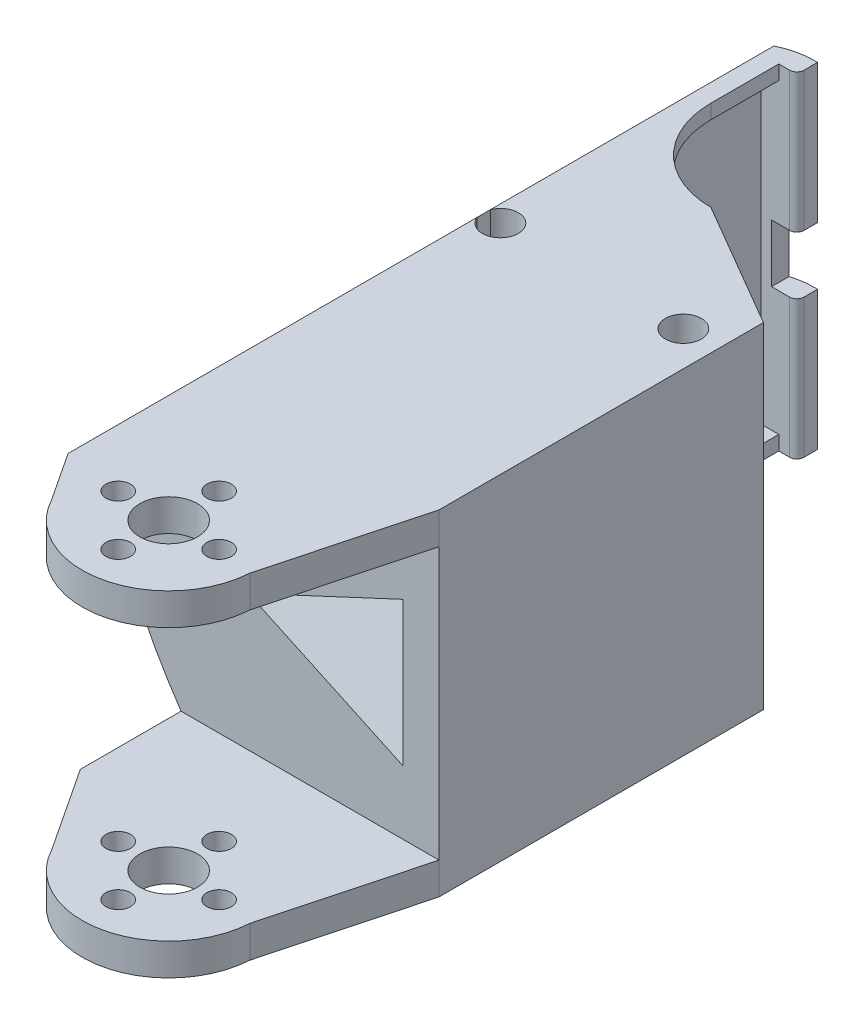
SolidWorks part; units mm, degrees
ref_plane "Front Plane" through (0, 0, 0) normal (0, 0, 1) x (1, 0, 0)
ref_plane "Top Plane" through (0, 0, 0) normal (0, 1, 0) x (1, 0, 0)
ref_plane "Right Plane" through (0, 0, 0) normal (1, 0, 0) x (0, 0, -1)
sketch "Sketch2" plane through (0, 0, 0) normal (0, 1, 0) x (1, 0, 0)
  line L0 (17.5, 0) -> (17.5, 37.7)
  line L1 (-15, 2.5) -> (15, 2.5)
  line L2 (-15, 2.5) -> (-15, 37.7)
  line L4 (15, 2.5) -> (15, 37.7)
  line L5 (17.5, 37.7) -> (15, 37.7)
  line L7 (-17.5, 37.7) -> (-17.5, 0)
  line L8 (-17.5, 0) -> (17.5, 0)
  line L10 (-17.5, 37.7) -> (-15, 37.7)
  point P4 (0, 2.5)
  point P12 (0, 0)
  dimension "D1" = 2.5
  dimension "D2" = 2.5
  dimension "D3" = 37.7
  dimension "D4" = 30
  dimension "D5" = 15
extrude "Boss-Extrude1" add sketch "Sketch2" along normal blind 32.5
sketch "Sketch4" plane through (0, 0, 0) normal (0, -1, 0) x (1, 0, 0)
  line L0 (-17.5, 0) -> (-17.5, -7.4438)
  line L8 (17.5, -7.4438) -> (17.5, 0)
  line L9 (17.5, 0) -> (-17.5, 0)
  line L10 (17.5, 0) -> (17.5, -37.7) construction
  line L13 (-17.5, -7.4438) -> (-17.5, -37.7)
  line L23 (-17.5, -37.7) -> (-15, -37.7)
  line L34 (-15, -37.7) -> (-15, -7.5)
  line L35 (-15, -2.5) -> (-15, -37.7) construction
  line L36 (-15, -7.5) -> (15, -7.5)
  line L37 (15, -37.7) -> (15, -2.5) construction
  line L38 (15, -7.5) -> (15, -37.7)
  line L39 (15, -37.7) -> (17.5, -37.7)
  line L40 (17.5, -37.7) -> (17.5, -7.4438)
  circle A2 centre (-12.6889, -4.95) radius 1.05
  circle A5 centre (12.6889, -4.95) radius 1.05
  dimension "D5" = 2.1
  dimension "D1" = 7.5
  dimension "D6" = 4.8111
  dimension "D7" = 4.95
  dimension "D8" = 4.8111
extrude "Boss-Extrude2" add sketch "Sketch4" along normal blind 2
sketch "Sketch7" plane through (0, -2, 0) normal (0, -1, 0) x (1, 0, 0)
  line L0 (-17.5, 0) -> (-17.5, -37.7)
  line L1 (-17.5, -37.7) -> (-15, -37.7)
  line L2 (-17.5, 0) -> (17.5, 0)
  line L4 (17.5, 0) -> (17.5, -37.7)
  line L5 (17.5, -37.7) -> (15, -37.7)
  line L6 (15, -37.7) -> (15, -7.5)
  line L7 (15, -7.5) -> (-15, -7.5)
  line L8 (-15, -7.5) -> (-15, -37.7)
  circle A2 centre (-12.6889, -4.95) radius 2.495
  circle A3 centre (12.6889, -4.95) radius 2.495
  dimension "D1" = 4.99
extrude "Wire spacing2" add sketch "Sketch7" along normal blind 3
sketch "Sketch8" plane through (0, -5, 0) normal (0, -1, 0) x (1, 0, 0)
  line L0 (-17.5, 0) -> (-17.5, -37.7)
  line L1 (-17.5, -37.7) -> (17.5, -37.7)
  line L2 (17.5, -37.7) -> (17.5, 0) construction
  line L3 (15, -37.7) -> (17.5, -37.7) construction
  line L4 (-17.5, 0) -> (17.5, 0)
  line L6 (17.5, 0) -> (17.5, -37.7)
  circle A0 centre (-12.6889, -4.95) radius 2.495
  circle A1 centre (12.6889, -4.95) radius 2.495
  circle A2 centre (12.6889, -4.95) radius 2.495 construction
  circle A3 centre (-12.6889, -4.95) radius 2.495 construction
extrude "Boss-Extrude6" add sketch "Sketch8" along normal blind 2
sketch "Sketch5" plane through (0, 32.5, 0) normal (0, 1, 0) x (1, 0, 0)
  line L0 (-9.939, 10) -> (-9.939, 2.5)
  line L9 (15, 2.5) -> (-15, 2.5) construction
  line L11 (-12.6889, 12) -> (-9.939, 10)
  line L13 (-17.5, 0) -> (17.5, 0) construction
  line L15 (-17.5, 0) -> (-17.5, 37.7)
  line L17 (12.6889, 12) -> (9.939, 10)
  line L20 (17.5, 0) -> (17.5, 37.7)
  line L21 (-9.939, 2.5) -> (9.939, 2.5)
  line L22 (9.939, 2.5) -> (9.939, 10)
  line L23 (-17.5, 0) -> (17.5, 0)
  line L24 (-12.6889, 12) -> (-15, 12)
  line L25 (-15, 37.7) -> (-15, 7.5) construction
  line L26 (-15, 12) -> (-15, 37.7)
  line L27 (-15, 37.7) -> (-17.5, 37.7)
  line L30 (17.5, 37.7) -> (15, 37.7)
  line L31 (15, 37.7) -> (15, 12)
  line L32 (15, 7.5) -> (15, 37.7) construction
  line L33 (15, 12) -> (12.6889, 12)
  circle A0 centre (-12.6889, 4.95) radius 1.05 construction
  circle A1 centre (-12.6889, 8.7) radius 1.05
  circle A2 centre (12.6889, 8.7) radius 1.05
  circle A3 centre (12.6889, 4.95) radius 1.05 construction
  dimension "D4" = 0
  dimension "D7" = 8.7
  dimension "D3" = 0
  dimension "D1" = 12
  dimension "D2" = 7.561
  dimension "D5" = 10
  dimension "D6" = 7.561
extrude "Boss-Extrude3" add sketch "Sketch5" along normal blind 2
sketch "Sketch9" plane through (0, 34.5, 0) normal (0, 1, 0) x (1, 0, 0)
  line L0 (-17.5, 0) -> (-17.5, 37.7)
  line L1 (-17.5, 37.7) -> (-15, 37.7)
  line L2 (-15, 37.7) -> (-15, 12)
  line L3 (-15, 12) -> (-12.6889, 12)
  line L4 (-12.6889, 12) -> (-9.939, 10)
  line L5 (-9.939, 10) -> (-9.939, 2.5)
  line L6 (-9.939, 2.5) -> (9.939, 2.5)
  line L7 (9.939, 2.5) -> (9.939, 10)
  line L8 (9.939, 10) -> (12.6889, 12)
  line L9 (12.6889, 12) -> (9.939, 10) construction
  line L10 (12.6889, 12) -> (15, 12)
  line L11 (15, 7.5) -> (15, 37.7) construction
  line L12 (15, 12) -> (15, 37.7)
  line L13 (15, 37.7) -> (17.5, 37.7)
  line L14 (17.5, 0) -> (17.5, 37.7) construction
  line L15 (17.5, 37.7) -> (15, 37.7) construction
  line L16 (17.5, 37.7) -> (17.5, 0)
  line L17 (17.5, 0) -> (-17.5, 0)
  line L18 (15, 12) -> (12.6889, 12) construction
  circle A0 centre (-12.6889, 8.7) radius 2.495
  circle A1 centre (12.6889, 8.7) radius 2.495
  dimension "D1" = 4.99
  dimension "D2" = 0
extrude "Wire spacing1" add sketch "Sketch9" along normal blind 3
sketch "Sketch10" plane through (0, 37.5, 0) normal (0, 1, 0) x (1, 0, 0)
  line L1 (-17.5, 37.7) -> (17.5, 37.7)
  line L2 (-17.5, 37.7) -> (-17.5, 0)
  line L3 (-17.5, 0) -> (17.5, 0)
  line L4 (17.5, 37.7) -> (17.5, 0)
  circle A0 centre (-12.6889, 8.7) radius 2.495
  circle A1 centre (12.6889, 8.7) radius 2.495
  circle A2 centre (-12.6889, 8.7) radius 2.495 construction
  circle A3 centre (12.6889, 8.7) radius 2.495 construction
extrude "Boss-Extrude8" add sketch "Sketch10" along normal blind 2
sketch "Sketch11" plane through (0, 39.5, 0) normal (0, 1, 0) x (1, 0, 0)
  line L0 (17.5, 37.7) -> (-17.5, 37.7) construction
  circle A0 centre (0, 37.7) radius 12.5
  dimension "D1" = 25
extrude "Cut-Extrude1" cut sketch "Sketch11" against normal through all
sketch "Sketch12" plane through (0, -7, 0) normal (0, -1, 0) x (1, 0, 0)
  line L4 (0, -25.2) -> (17.5, -15)
  line L5 (17.5, -37.7) -> (17.5, 0) construction
  line L6 (17.5, -15) -> (17.5, -47.4845)
  line L7 (17.5, -47.4845) -> (0, -25.2)
  line L8 (17.5, 0) -> (-17.5, 0) construction
  arc A1 (12.5, -37.7) -> (-12.5, -37.7) centre (0, -37.7) ccw construction
  dimension "D1" = 15
extrude "Cut-Extrude2" cut sketch "Sketch12" against normal through all
sketch "Sketch13" plane through (0, 0, 0) normal (0, 0, 1) x (1, 0, 0)
  line L0 (17.5, -7) -> (-17.5, -7) construction
  line L1 (17.5, 39.5) -> (-27.5, 39.5)
  line L2 (17.5, 39.5) -> (17.5, -7)
  line L3 (17.5, -7) -> (-27.5, -7)
  line L4 (-27.5, 39.5) -> (-27.5, -7)
  line L5 (-17.5, 39.5) -> (-17.5, -7) construction
  dimension "D1" = 10
extrude "Boss-Extrude9" add sketch "Sketch13" along normal blind 30
sketch "Sketch15" plane through (0, 0, 0) normal (0, 0, -1) x (-1, 0, 0)
  line L0 (17.5, -7) -> (12.5, -7) construction
  line L1 (27.5, 39.5) -> (15, 39.5)
  line L2 (27.5, 39.5) -> (27.5, -7)
  line L3 (27.5, -7) -> (15, -7)
  line L4 (15, 39.5) -> (15, -7)
extrude "Boss-Extrude10" add sketch "Sketch15" along normal blind 50
sketch "Sketch18" plane through (0, -7, 0) normal (0, -1, 0) x (1, 0, 0)
  line L0 (12.5, 35) -> (12.5, 30)
  line L1 (12.5, 30) -> (-12.5, 30)
  line L2 (-12.5, 35) -> (-12.5, 30)
  line L3 (12.5, 35) -> (9.3675, 42.5)
  line L4 (-9.3675, 42.5) -> (-12.5, 35)
  line L5 (-27.5, 30) -> (17.5, 30) construction
  circle A0 centre (0, 50) radius 4
  arc A1 (9.3675, 42.5) -> (-9.3675, 42.5) centre (0, 50) ccw
  circle A2 centre (0, 43) radius 1.7
  circle A3 centre (-7, 50) radius 1.7
  circle A4 centre (0, 57) radius 1.7
  circle A5 centre (7, 50) radius 1.7
  point P11 (7.7726, 26.3901)
  point P12 (0, 30)
  dimension "D3" = 8
  dimension "D5" = 12
  dimension "D7" = 3.4
  dimension "D1" = 25
  dimension "D2" = 20
  dimension "D4" = 5
  dimension "D6" = 12.5
  dimension "D8" = 7
  dimension "D9" = 7
  dimension "D10" = 7
  dimension "D11" = 7
  dimension "D12" = 0
  dimension "D13" = 0
extrude "Boss-Extrude11" add sketch "Sketch18" against normal up to surface (46.5 mm away) up to face at (-12.5969, 39.5, -8.7)
sketch "Sketch22" plane through (0, -7, 0) normal (0, -1, 0) x (1, 0, 0)
  line L0 (-27.5, 30) -> (-9.3341, 57.5416)
  line L1 (-9.3341, 57.5416) -> (-9.3341, 30)
  line L2 (-9.3341, 30) -> (-27.5, 30)
  line L4 (17.5, 30) -> (10.749, 55.3347)
  line L5 (10.749, 55.3347) -> (7.9223, 30)
  line L6 (7.9223, 30) -> (17.5, 30)
  arc A0 (9.3675, 42.5) -> (-9.3675, 42.5) centre (0, 50) ccw construction
extrude "Boss-Extrude13" add sketch "Sketch22" against normal up to surface (46.5 mm away) up to face at (-12.5969, 39.5, -8.7)
sketch "Sketch21" plane through (-27.5, 0, 0) normal (-1, 0, 0) x (0, 0, 1)
  line L1 (107.4125, 35.075) -> (30, 35.075)
  line L2 (107.4125, 35.075) -> (107.4125, -2.575)
  line L3 (107.4125, -2.575) -> (30, -2.575)
  line L4 (30, 35.075) -> (30, -2.575)
  line L6 (-50, -7) -> (-50, 39.5) construction
  line L7 (30, 39.5) -> (30, -7) construction
  point P6 (-50, 16.25)
  point P7 (30, 16.25)
  dimension "D1" = 37.65
  dimension "D2" = 0
extrude "Cut-Extrude3" cut sketch "Sketch21" against normal through all
sketch "Sketch26" plane through (0, 39.5, 0) normal (0, 1, 0) x (1, 0, 0)
  line L0 (-27.5, -30) -> (-27.5, 50) construction
  line L1 (-27.5, 29.3872) -> (-27.5, 50)
  line L2 (-27.5, 50) -> (-15, 50)
  spline S0 degree 2 poles (-15, 50) (-23.5947, 41.1535) (-27.5, 29.3872) knots 0 0 0 1 1 1
extrude "Cut-Extrude5" cut sketch "Sketch26" against normal through all
sketch "Sketch24" plane through (0, 0, 0) normal (0, 0, -1) x (-1, 0, 0)
  line L4 (15, -7) -> (27.5, -7)
  line L5 (27.5, -7) -> (27.5, 16.25)
  spline S0 degree 2 poles (27.5, 16.25) (23.3985, 3.4824) (15, -7) knots 0 0 0 1 1 1
extrude "Cut-Extrude4" cut sketch "Sketch24" against normal through all both and the other way through all
ref_plane "Plane1" through (0, 16.25, 0) normal (0, -1, 0) x (-1, 0, 0)
mirror "Mirror1" about plane through (0, 16.25, 0) normal (0, -1, 0) of "Cut-Extrude4"
sketch "Sketch27" plane through (0, 0, -2.5) normal (0, 0, -1) x (-1, 0, 0)
  line L0 (-12.5, 26.25) -> (8.9451, 16.25)
  line L1 (-17.875, 16.25) -> (17.875, 16.25) construction
  line L2 (8.9451, 16.25) -> (-12.5, 6.25)
  line L4 (-12.5, 6.25) -> (-12.5, 26.25)
  line L5 (-15, 32.5) -> (-15, 0) construction
  point P7 (-12.5, 16.25)
  dimension "D1" = 50
  dimension "D2" = 20
  dimension "D3" = 2.5
extrude "Cut-Extrude6" cut sketch "Sketch27" against normal through all
sketch "Sketch28" plane through (0, 39.5, 0) normal (0, 1, 0) x (1, 0, 0)
  line L0 (-15, 37.7) -> (-15, 50)
  line L1 (-15, 50) -> (-10, 50)
  line L2 (-10, 50) -> (-10, 47.127)
  line L3 (-10, 47.127) -> (-12.5, 47.127)
  line L4 (-12.5, 47.127) -> (-12.5, 37.7)
  line L5 (-15, 37.7) -> (-12.5, 37.7)
  dimension "D1" = 2.5
extrude "Boss-Extrude14" add sketch "Sketch28" against normal up to surface (46.5 mm away) up to face at (-3.2058, -7, 7.0935)
fillet "Fillet2" radius 10 1 edges at (-15, 16.25, -50)
sketch "Sketch29" plane through (0, 0, -37.7) normal (0, 0, 1) x (1, 0, 0)
  line L1 (-15, 37.5) -> (-12.5, 37.5)
  line L2 (-15, 37.5) -> (-15, -5)
  line L3 (-15, -5) -> (-12.5, -5)
  line L4 (-12.5, 37.5) -> (-12.5, -5)
extrude "Cut-Extrude8" cut sketch "Sketch29" against normal up to surface (9.427 mm away) up to face at (-11.25, 16.25, -47.127)
fillet "Fillet3" radius 1 1 edges at (-10, 16.25, -47.127)
sketch "Sketch30" plane through (0, 0, -47.127) normal (0, 0, 1) x (1, 0, 0)
  line L0 (-17.875, 16.25) -> (17.875, 16.25) construction
  line L1 (-6.1884, 20.25) -> (-13.5, 20.25)
  line L2 (-6.1884, 20.25) -> (-6.1884, 12.25)
  line L3 (-6.1884, 12.25) -> (-13.5, 12.25)
  line L4 (-13.5, 20.25) -> (-13.5, 12.25)
  line L5 (-11, -7) -> (-11, 39.5) construction
  point P4 (-13.5, 16.25)
  dimension "D1" = 8
  dimension "D2" = 2.5
extrude "Cut-Extrude9" cut sketch "Sketch30" against normal blind 22.5
